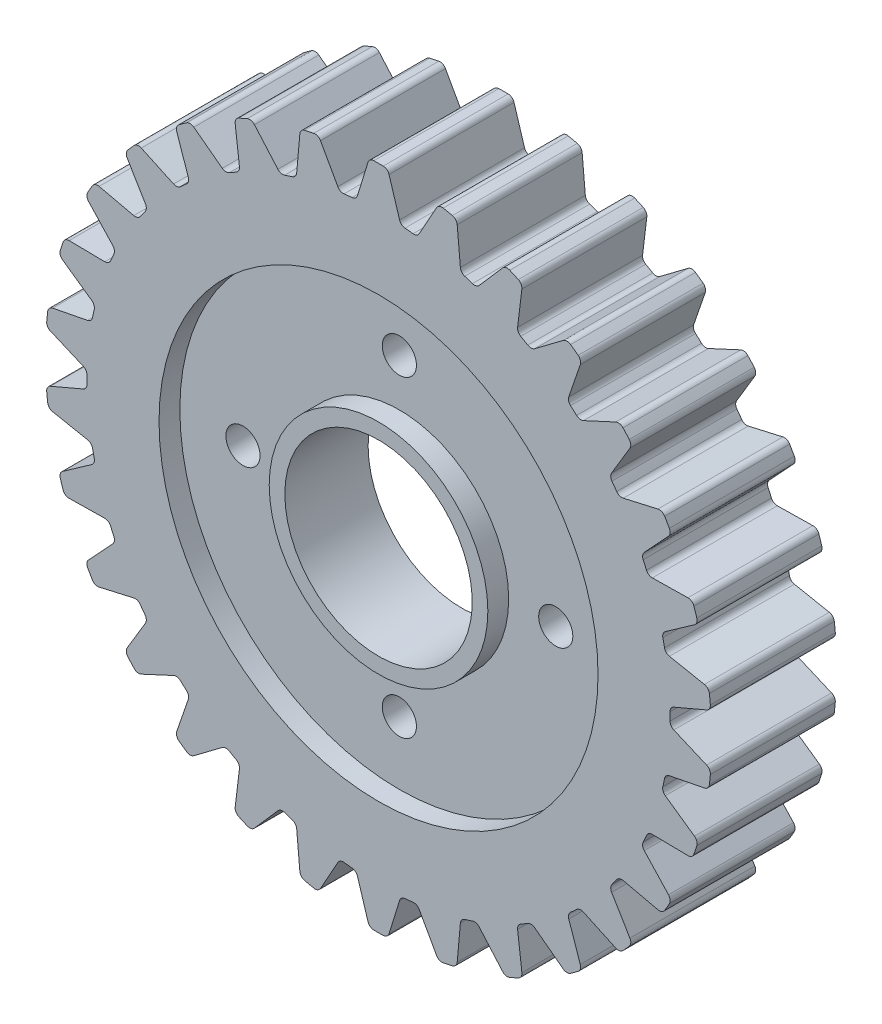
SolidWorks part; units mm, degrees
ref_plane "Front Plane" through (0, 0, 0) normal (0, 0, 1) x (1, 0, 0)
ref_plane "Top Plane" through (0, 0, 0) normal (0, 1, 0) x (1, 0, 0)
ref_plane "Right Plane" through (0, 0, 0) normal (1, 0, 0) x (0, 0, -1)
sketch "Sketch1" plane through (0, 0, 0) normal (0, 0, 1) x (1, 0, 0)
  circle A2 centre (0, 0) radius 14
  dimension "Blank diameter" = 28
extrude "Body" add sketch "Sketch1" against normal blind 6
sketch "Sketch2" plane through (0, 0, 0) normal (0, 0, 1) x (1, 0, 0)
  line L0 (0, 26.3446) -> (0, 3.6554) construction
  line L1 (-0.755, 14.981) -> (-1.0697, 13.9591)
  line L2 (-0.755, 14.981) -> (-0.4431, 15.9939)
  line L3 (0.755, 14.981) -> (1.0697, 13.9591)
  line L4 (0.755, 14.981) -> (0.4431, 15.9939)
  line L5 (0, 0) -> (-2.2254, 44.1563) construction
  line L6 (0, 0) -> (2.1494, 42.6484) construction
  arc A0 (0.4431, 15.9939) -> (-0.4431, 15.9939) centre (0, 0) ccw
  arc A1 (0.755, 14.981) -> (-0.755, 14.981) centre (0, 0) ccw construction
  arc A2 (1.0697, 13.9591) -> (-1.0697, 13.9591) centre (0, 0) ccw
  point P1 (0, 15)
  dimension "D2" = 20
  dimension "D3" = 20
  dimension "Full diameter" = 32
  dimension "Pitch diameter" = 30
  dimension "Blank diameter" = 28
  dimension "Tooth width PCD" = 1.51
extrude "Tooth" add sketch "Sketch2" against normal blind 6
fillet "Tooth Fillet" radius 0.3 4 edges at (-0.4431, 15.9939, -3) (-1.0697, 13.9591, -3) (0.4431, 15.9939, -3) (1.0697, 13.9591, -3)
pattern_circular "Tooth Pattern" count 30 over 360 about axis through (0, 0, 0) along (0, 0, 1) of "Tooth", "Tooth Fillet"
ref_axis "Axis1" through (0, 0, 0) along (0, 0, -1)
sketch "Sketch3" plane through (0, 0, 0) normal (0, 0, 1) x (1, 0, 0)
  circle A0 centre (0, 0) radius 5.25
  circle A1 centre (0, 0) radius 12
  dimension "Plastic boss" = 10.5
  dimension "Resses" = 24
extrude "Resses1" cut sketch "Sketch3" against normal blind 1
sketch "Sketch4" plane through (0, 0, -6) normal (0, 0, -1) x (-1, 0, 0)
  circle A0 centre (0, 0) radius 12
  circle A1 centre (0, 0) radius 5.25
  dimension "Plastic boss" = 10.5
  dimension "Resses" = 24
extrude "Resses2" cut sketch "Sketch4" against normal blind 1
sketch "Sketch5" plane through (0, 0, -6) normal (0, 0, -1) x (-1, 0, 0)
  circle A0 centre (0, 0) radius 5
  dimension "D1" = 10
extrude "Brass boss" [suppressed] add sketch "Sketch5" along normal blind 5.7
sketch "Sketch6" [suppressed] plane through (0, 0, -11.7) normal (0, 0, -1) x (-1, 0, 0)
  circle A0 centre (0, 0) radius 2
  dimension "D1" = 4
extrude "Bore" [suppressed] cut sketch "Sketch6" against normal through all
sketch "Sketch7" plane through (0, 0, 0) normal (0, 1, 0) x (1, 0, 0)
  circle A0 centre (0, 8.8626) radius 1
  dimension "D1" = 2
extrude "Grub screw" [suppressed] cut sketch "Sketch7" against normal through all
sketch "Sketch8" plane through (0, 0, -5) normal (0, 0, -1) x (-1, 0, 0)
  circle A0 centre (-0.8321, 10.5608) radius 1.8434
extrude "Extrude1" [suppressed] add sketch "Sketch8" along normal blind 5
sketch "Sketch9" plane through (0, 0, -6) normal (0, 0, -1) x (-1, 0, 0)
  circle A0 centre (0, 0) radius 10.541
  dimension "D1" = 21.082
extrude "Cut-Extrude1" cut sketch "Sketch9" against normal blind 2
sketch "Sketch10" plane through (0, 0, -6) normal (0, 0, -1) x (-1, 0, 0)
  circle A0 centre (0, 0) radius 10.541 construction
  circle A1 centre (0, 0) radius 10.541
  circle A2 centre (0, 0) radius 12.541
  dimension "D1" = 2
extrude "Boss-Extrude1" add sketch "Sketch10" against normal up to surface (6 mm away) up to face at (12, 0, 0)
sketch "Sketch11" plane through (0, 0, -4) normal (0, 0, -1) x (-1, 0, 0)
  circle A0 centre (0, 0) radius 4.5
  circle A1 centre (0, 7.51) radius 0.82
  circle A2 centre (7.51, 0) radius 0.82
  circle A3 centre (0, -7.51) radius 0.82
  circle A4 centre (-7.51, 0) radius 0.82
  point P14 (0, 0)
  dimension "D1" = 9
  dimension "D2" = 1.64
  dimension "D3" = 7.51
  dimension "D4" = 4
extrude "Cut-Extrude2" cut sketch "Sketch11" against normal through all
